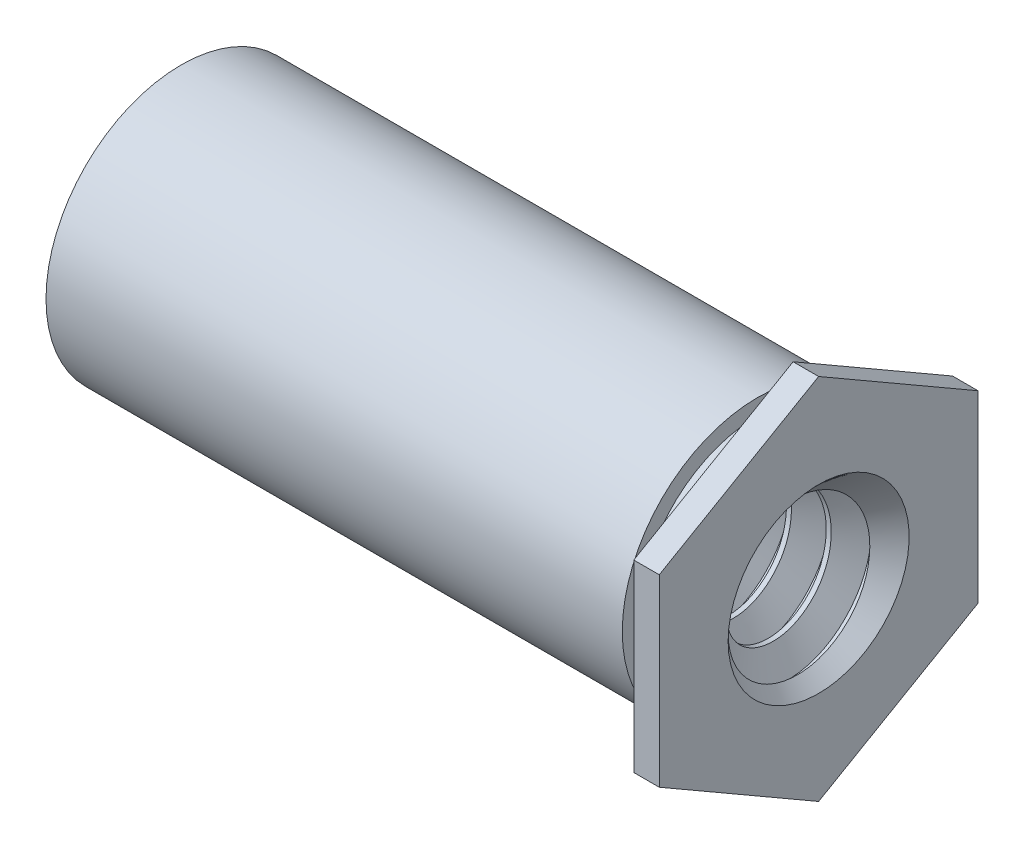
SolidWorks part; units mm, degrees
ref_plane "Front Plane" through (0, 0, 0) normal (0, 0, 1) x (1, 0, 0)
ref_plane "Top Plane" through (0, 0, 0) normal (0, 1, 0) x (1, 0, 0)
ref_plane "Right Plane" through (0, 0, 0) normal (1, 0, 0) x (0, 0, -1)
sketch "Sketch1" plane through (0, 0, 0) normal (0, 0, 1) x (1, 0, 0)
  line L0 (-6.35, 0) -> (6.35, 0) construction
  line L1 (-6.35, 2.6924) -> (-6.35, -2.6924) construction
  line L2 (-1.5875, 1.7526) -> (-1.5875, -1.7526) construction
  line L3 (6.35, 3.175) -> (6.35, -3.175) construction
  line L4 (-1.5875, 1.7526) -> (6.35, 1.7526) construction
  line L5 (-1.5875, -1.7526) -> (6.35, -1.7526) construction
  point P4 (-1.5875, 0)
  point P10 (5.842, 0)
  point P11 (5.1308, 0)
  dimension "D1" = 6.35
  dimension "OD" = 5.3848
  dimension "Length" = 12.7
  dimension "Thread Height" = 7.9375
  dimension "Thread Size" = 3.5052
  dimension "D3" = 0.7112
  dimension "D4" = 0.508
ref_plane "Plane1" through (-6.35, 0, 0) normal (1, 0, 0) x (0, 0, -1)
sketch "Sketch2" plane through (-6.35, 0, 0) normal (1, 0, 0) x (0, 0, -1)
  circle A0 centre (0, 0) radius 2.6924
  circle A1 centre (0, 0) radius 1.7526
extrude "Extrude1" add sketch "Sketch2" along normal up to vertex (12.7 mm away) up to point (6.35, 0, 0)
sketch "Sketch3" plane through (6.35, 0, 0) normal (1, 0, 0) x (0, 0, -1)
  line L1 (0, 3.6662) -> (-3.175, 1.8331)
  line L2 (-3.175, 1.8331) -> (-3.175, -1.8331)
  line L3 (-3.175, -1.8331) -> (0, -3.6662)
  line L4 (0, -3.6662) -> (3.175, -1.8331)
  line L5 (3.175, -1.8331) -> (3.175, 1.8331)
  line L6 (3.175, 1.8331) -> (0, 3.6662)
  circle A0 centre (0, 0) radius 3.175 construction
  circle A1 centre (0, 0) radius 1.7526 construction
  circle A2 centre (0, 0) radius 1.7526
extrude "Extrude2" add sketch "Sketch3" against normal up to vertex (0.508 mm away) up to point (5.842, 0, 0)
sketch "Sketch4" plane through (5.842, 0, 0) normal (-1, 0, 0) x (0, 0, 1)
  circle A0 centre (0, 0) radius 2.3749
  circle A1 centre (0, 0) radius 2.6924 construction
  circle A2 centre (0, 0) radius 2.6924
  dimension "D1" = 0.3175
extrude "Extrude3" cut sketch "Sketch4" along normal up to vertex (0.7112 mm away) up to point (5.1308, 0, 0)
sketch "Sketch6" plane through (6.35, 0, 0) normal (-1, 0, 0) x (0, 0, 1)
  circle A0 centre (0, 0) radius 1.7526 construction
  circle A2 centre (0, 0) radius 1.7526
curve "Helix/Spiral1" pitch 0.7937 height 13.4937 turns 17 parameters "Pitch"=0.7937
sketch "Sketch7" plane through (0, 0, 0) normal (0, 0, 1) x (1, 0, 0)
  line L0 (6.35, 1.7526) -> (7.0445, 1.7526)
  line L1 (6.35, 1.7526) -> (6.6477, 1.237)
  line L2 (6.6477, 1.237) -> (6.7469, 1.237)
  line L3 (6.7469, 1.237) -> (7.0445, 1.7526)
  line L4 (6.6973, 1.237) -> (6.6973, 1.7526) construction
  line L5 (6.4988, 1.4948) -> (6.8957, 1.4948) construction
  line L6 (6.35, 1.7526) -> (6.35, -1.7526) construction
  dimension "D1" = 60
  dimension "D2" = 0.0992
  dimension "D3" = 0.3969
sweep "Sweep1" add profiles "Sketch7" path "Helix/Spiral1"
sketch "Sketch8" plane through (6.35, 0, 0) normal (-1, 0, 0) x (0, 0, 1)
  circle A3 centre (0, 0) radius 1.8034
  circle A4 centre (0, 0) radius 1.8034
  dimension "D1" = 0.0508
extrude "Extrude6" cut sketch "Sketch8" against normal through all and the other way through all draft 45
sketch "Sketch9" plane through (-6.35, 0, 0) normal (1, 0, 0) x (0, 0, -1)
  circle A1 centre (0, 0) radius 1.8034
  circle A2 centre (0, 0) radius 1.8034
  dimension "D1" = 0
extrude "Extrude7" cut sketch "Sketch9" along normal through all draft 45 and the other way through all
sketch "Sketch10" plane through (-6.35, 0, 0) normal (1, 0, 0) x (0, 0, -1)
  circle A0 centre (0, 0) radius 1.237 construction
  circle A1 centre (0, 0) radius 1.8034
  circle A2 centre (0, 0) radius 1.8034
  circle A3 centre (0, 0) radius 1.197
  dimension "D1" = 0
  dimension "D2" = 0.0401
extrude "Extrude8" add sketch "Sketch10" along normal offset from surface (4.7625 mm away) 7.9375 up to face at (6.35, 0, 0)
equation "\"D2@Sketch7\" = \"Pitch@Helix/Spiral1\"*.125"
equation "\"D3@Sketch7\" = \"Pitch@Helix/Spiral1\"*.5"
equation "\"D3@Helix/Spiral1\" = \"Length@Sketch1\"+\"Pitch@Helix/Spiral1\""
